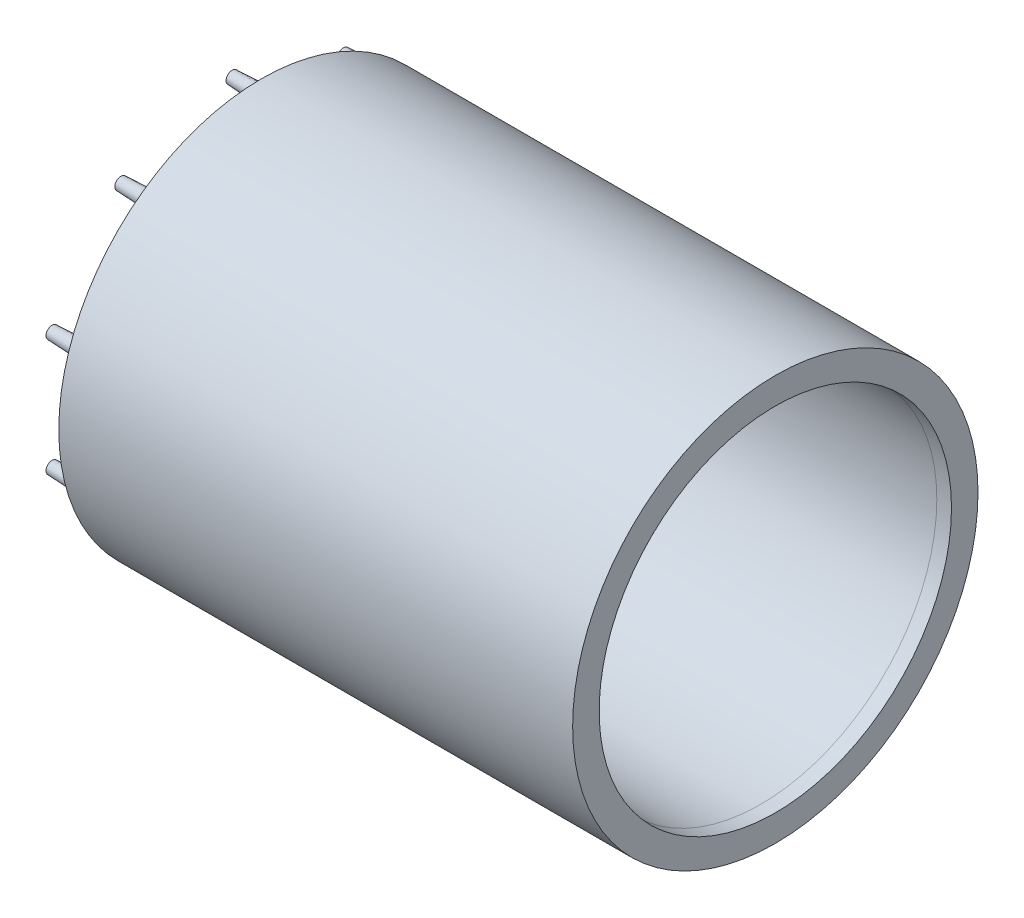
SolidWorks part; units mm, degrees
ref_plane "Front Plane" through (0, 0, 0) normal (0, 0, 1) x (1, 0, 0)
ref_plane "Top Plane" through (0, 0, 0) normal (0, 1, 0) x (1, 0, 0)
ref_plane "Right Plane" through (0, 0, 0) normal (1, 0, 0) x (0, 0, -1)
sketch "Sketch1" plane through (0, 0, 0) normal (0, 0, 1) x (1, 0, 0)
  line L2 (0, -76.2) -> (-921.7152, -76.2) construction
  line L3 (6.35, 6.35) -> (6.35, 0)
  line L4 (-259.8125, 11.4606) -> (6.35, 11.4606)
  line L5 (0, 0) -> (6.35, 0)
  line L6 (6.35, 6.35) -> (6.35, -76.2) construction
  line L7 (0, 0) -> (0, -76.2) construction
  line L8 (-921.7152, -58.5997) -> (-928.0652, -58.5997)
  line L9 (-928.0652, -58.5997) -> (-928.0652, -76.2) construction
  line L10 (-921.7152, -58.5997) -> (-921.7152, -76.2) construction
  line L11 (6.35, 11.4606) -> (6.35, 6.35)
  arc A0 (-254, 2.1118) -> (-248.4137, -0.891) centre (-248.6021, 5.4563) ccw
  arc A2 (-916.3053, -52.3197) -> (-921.7152, -58.5997) centre (-915.3652, -58.5997) ccw
  arc A4 (-254, 2.1118) -> (-259.6052, 5.114) centre (-259.3979, -1.2327) ccw
  arc A6 (-248.6021, 5.4563) -> (-248.6021, 5.4563) centre (-248.6021, 5.4563) ccw
  arc A7 (-248.6021, 5.4563) -> (-259.8125, 11.4606) centre (-259.3979, -1.2327) ccw
  arc A8 (-917.2454, -46.0396) -> (-928.0652, -58.5997) centre (-915.3652, -58.5997) ccw
  spline S0 degree 3 poles (0, 0) (-50.8, 0) (-101.6, 0) (-157.1824, 0) (-166.7471, 0) (-181.0943, 0) (-190.659, 0) (-199.5851, 0) (-207.8726, 0) (-220.3048, -0.155) (-228.5897, -0.3615) (-235.0947, -0.5237) (-239.8196, -0.6415) (-245.0466, -0.7915) (-247.9113, -0.876) (-248.4137, -0.891) knots 0.761574 0.761574 0.761574 0.761574 0.907842 0.907842 0.921611 0.935381 0.949151 0.949151 0.961082 0.973013 0.984944 0.984944 0.991748 0.998553 1 1 1 1
  spline S1 degree 1 poles (6.35, 6.35) (-248.6021, 5.4563) knots 0 0 1 1 construction
  spline S2 degree 3 poles (-259.6052, 5.114) (-267.1277, 4.8682) (-283.426, 4.2857) (-317.2703, 2.8805) (-361.13, 0.7112) (-431.2755, -3.372) (-501.3729, -8.2669) (-571.4145, -13.8917) (-623.9147, -18.4777) (-676.3803, -23.4393) (-728.8057, -28.7991) (-772.4536, -33.6275) (-807.3418, -37.7392) (-833.4907, -40.9589) (-859.6194, -44.3289) (-885.7239, -47.8693) (-904.6125, -50.5779) (-914.801, -52.0945) (-916.3053, -52.3197) knots 0.121539 0.121539 0.121539 0.121539 0.143123 0.168303 0.218664 0.269025 0.369746 0.420107 0.470467 0.520828 0.571189 0.62155 0.64673 0.67191 0.697091 0.722271 0.747451 0.751814 0.751814 0.751814 0.751814
  spline S3 degree 1 poles (-259.8125, 11.4606) (-917.2454, -46.0396) knots 0 0 1 1 construction
  spline S4 degree 3 poles (6.35, 6.35) (-14.881, 6.35) (-57.3424, 6.3506) (-110.4226, 6.3484) (-152.8795, 6.3528) (-179.4314, 6.3414) (-200.6356, 6.3648) (-216.6826, 6.282) (-232.6614, 5.8947) (-243.2867, 5.614) (-248.6021, 5.4563) knots 0.75548 0.75548 0.75548 0.75548 0.81661 0.87774 0.908305 0.93887 0.954152 0.969435 0.984717 1 1 1 1
  spline S5 degree 3 poles (-259.8125, 11.4606) (-287.3121, 10.5623) (-342.298, 8.1716) (-452.1401, 1.8335) (-589.2803, -8.5121) (-726.1766, -21.7709) (-835.4658, -34.5887) (-890.027, -41.9652) (-917.2454, -46.0396) knots 0.121539 0.121539 0.121539 0.121539 0.200324 0.279108 0.436676 0.594245 0.673029 0.751814 0.751814 0.751814 0.751814
revolve "Revolve1" add sketch "Sketch1" angle 360 about L2 region at (-124.3289, 8.8839, 0) region at (-3.0204, 3.175, 0)
ref_plane "Plane1" through (-215.9, 0, 0) normal (1, 0, 0) x (0, 0, -1)
sketch "Sketch2" plane through (-215.9, 0, 0) normal (1, 0, 0) x (0, 0, -1)
  circle A0 centre (0, -76.2) radius 87.6606 construction
  circle A1 centre (0, -76.2) radius 87.6606 construction
  circle A2 centre (0, -76.2) radius 110.1147
extrude "Cut-Extrude1" cut sketch "Sketch2" against normal through all contours A2 region at (-215.9, -76.2, 0)
sketch "Sketch3" plane through (-215.9, 0, 0) normal (-1, 0, 0) x (0, 0, 1)
  circle A0 centre (0, -76.2) radius 76.0918 construction
  circle A1 centre (0, -76.2) radius 87.6606 construction
  circle A2 centre (0, -76.2) radius 76.0918
  circle A3 centre (0, -76.2) radius 87.6606
  circle A4 centre (0, -76.2) radius 81.8762 construction
  circle A5 centre (0, 5.6762) radius 3.175
  circle A6 centre (48.1256, -9.9608) radius 3.175
  circle A7 centre (77.8689, -50.8989) radius 3.175
  circle A8 centre (77.8689, -101.5011) radius 3.175
  circle A9 centre (48.1256, -142.4392) radius 3.175
  circle A10 centre (0, -158.0762) radius 3.175
  circle A11 centre (-48.1256, -142.4392) radius 3.175
  circle A12 centre (-77.8689, -101.5011) radius 3.175
  circle A13 centre (-77.8689, -50.8989) radius 3.175
  circle A14 centre (-48.1256, -9.9608) radius 3.175
  point P30 (0, -76.2)
  dimension "D1" = 11.5687
  dimension "D2" = 5.7844
  dimension "D3" = 6.35
  dimension "D4" = 10
extrude "Boss-Extrude1" add sketch "Sketch3" along normal blind 12.7 draft 2.5 contours A13 | A14 | A5 | A6 | A7 | A8 | A9 | A10 | A11 | A12 region at (-215.9, 5.6762, 0) region at (-215.9, -9.9608, 48.1256) region at (-215.9, -50.8989, 77.8689) region at (-215.9, -101.5011, 77.8689) region at (-215.9, -142.4392, 48.1256) region at (-215.9, -158.0762, 0) region at (-215.9, -142.4392, -48.1256) region at (-215.9, -101.5011, -77.8689) region at (-215.9, -50.8989, -77.8689) region at (-215.9, -9.9608, -48.1256)
